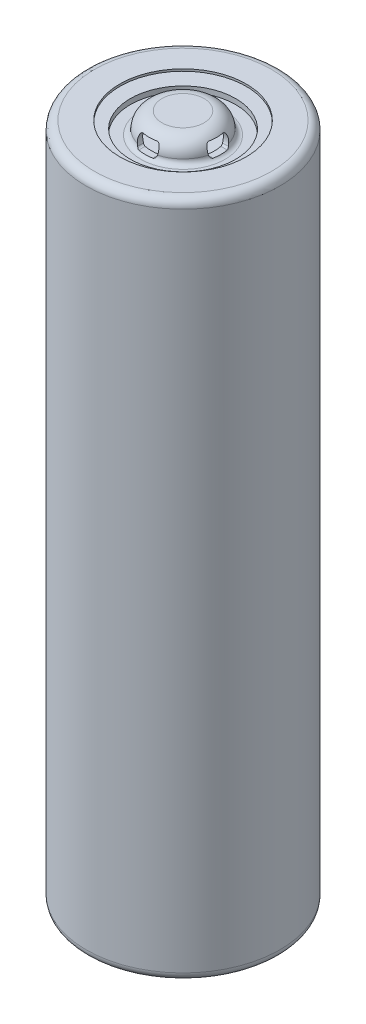
SolidWorks part; units mm, degrees
ref_plane "Front Plane" through (0, 0, 0) normal (0, 0, 1) x (1, 0, 0)
ref_plane "Top Plane" through (0, 0, 0) normal (0, 1, 0) x (1, 0, 0)
ref_plane "Right Plane" through (0, 0, 0) normal (1, 0, 0) x (0, 0, -1)
sketch "Sketch1" plane through (0, 0, 0) normal (0, 1, 0) x (1, 0, 0)
  circle A0 centre (0, 0) radius 9
  dimension "D1" = 18
extrude "Boss-Extrude1" add sketch "Sketch1" along normal blind 60
fillet "Fillet1" radius 1 2 edges at (0, 60, 9) (0, 0, 9)
sketch "Sketch2" plane through (0, 60, 0) normal (0, 1, 0) x (1, 0, 0)
  circle A0 centre (0, 0) radius 7
  dimension "D1" = 14
extrude "Boss-Extrude2" add sketch "Sketch2" along normal blind 2
fillet "Fillet2" radius 1 1 edges at (0, 62, 7)
sketch "Sketch4" plane through (0, 0, 0) normal (0, 0, 1) x (1, 0, 0)
  line L0 (0, 65) -> (3.5, 65)
  line L1 (3.5, 65) -> (3.5, 63)
  line L2 (3.5, 63) -> (8, 63)
  line L3 (8, 63) -> (8, 62)
  line L4 (6, 62) -> (-6, 62) construction
  line L5 (8, 62) -> (0, 62) construction
  line L6 (0, 62) -> (0, 65) construction
  line L7 (6, 62) -> (-6, 62) construction
  line L8 (0, 65) -> (0, 64.5) construction
  line L9 (0, 64.5) -> (3, 64.5)
  line L10 (3, 64.5) -> (3, 62.5)
  line L11 (3, 62.5) -> (5, 62.5)
  line L12 (5, 62.5) -> (5, 62)
  line L13 (5, 62) -> (8, 62) construction
  line L14 (5, 62) -> (8, 62)
  line L15 (0, 65) -> (0, 64.5)
  point P2 (1.75, 65)
  dimension "D1" = 65
  dimension "D2" = 8
  dimension "D3" = 3.5
  dimension "D4" = 2
  dimension "D5" = 0.5
  dimension "D6" = 0.5
  dimension "D7" = 0.5
  dimension "D8" = 3
revolve "Revolve1" add sketch "Sketch4" angle 360 about L6
fillet "Fillet3" radius 1.5 1 edges at (0, 65, -3.5)
fillet "Fillet4" radius 0.5 1 edges at (0, 63, -3.5)
fillet "Fillet5" radius 0.5 2 edges at (0, 62, -8) (0, 63, -8)
sketch "Sketch5" plane through (0, 0, 0) normal (0, 0, 1) x (1, 0, 0)
  line L0 (7.5, 63) -> (-7.5, 63) construction
  line L1 (8, 63.5) -> (5, 63.5)
  line L2 (8, 63.5) -> (8, 63)
  line L3 (8, 63) -> (5, 63)
  line L4 (5, 63.5) -> (5, 63)
  line L5 (0, 63) -> (0, 63.5) construction
  line L6 (0, 63.5) -> (5, 63.5) construction
  line L7 (0, 63) -> (5, 63) construction
  dimension "D1" = 0.5
  dimension "D2" = 5
revolve "Revolve2 isolation" add sketch "Sketch5" angle 360 about L5
sketch "Sketch6" plane through (0, 0, 0) normal (1, 0, 0) x (0, 0, -1)
  line L0 (7, 62) -> (7, 61)
  line L1 (7, 61) -> (8.8, 61)
  line L2 (8.8, 61) -> (8.8, 64)
  line L3 (8.8, 64) -> (7, 64)
  line L4 (7, 64) -> (7, 63.5)
  line L5 (8, 63.5) -> (-8, 63.5) construction
  line L6 (7, 63.5) -> (8.5, 63.5)
  line L7 (8.5, 63.5) -> (8.5, 61.3)
  line L10 (0, 0) -> (0, 65) construction
  line L11 (2, 65) -> (-2, 65) construction
  line L12 (7, 62) -> (7.3, 62)
  line L13 (7.3, 62) -> (7.3, 61.3)
  line L14 (7.3, 61.3) -> (8.5, 61.3)
  line L15 (8, 60) -> (-8, 60) construction
  point P3 (8.2057, 60.5263)
  dimension "D1" = 0.3
  dimension "D2" = 0.3
  dimension "D3" = 1
  dimension "D4" = 7
  dimension "D5" = 0.3
  dimension "D6" = 8.8
  dimension "D7" = 1
revolve "Revolve4 crimp" add sketch "Sketch6" angle 360 about L10
fillet "Fillet6" radius 0.8 3 edges at (0, 61, -8.8) (0, 64, -8.8) (0, 64, -7)
fillet "Fillet7" radius 0.3 1 edges at (0, 61, -7)
sketch "Sketch7" plane through (0, 0, 0) normal (1, 0, 0) x (0, 0, -1)
  line L0 (2, 65) -> (-2, 65) construction
  line L1 (0, 65) -> (0, 0) construction
  line L3 (-0.8, 63.2) -> (0.8, 63.2)
  line L4 (-0.3603, 63.2377) -> (-0.3603, 63.9235) construction
  line L5 (-0.8, 64.4) -> (0.8, 64.4)
  line L6 (1, 63.4571) -> (1, 65.3608) construction
  line L7 (-0.3603, 63.2377) -> (1, 65.3608) construction
  line L8 (-0.3603, 63.9235) -> (1, 63.4571) construction
  circle A1 centre (0, 63.8) radius 1 construction
  arc A2 (-0.8, 64.4) -> (-0.8, 63.2) centre (0, 63.8) ccw
  arc A3 (0.8, 64.4) -> (0.8, 63.2) centre (0, 63.8) cw
  dimension "D1" = 2
  dimension "D2" = 1.2
  dimension "D3" = 1.2
  dimension "D4" = 0.6
extrude "Cut-Extrude1" cut sketch "Sketch7" against normal blind 4
fillet "Fillet8" radius 0.25 4 edges at (-2.9949, 64.4, 0.8) (-2.9949, 64.4, -0.8) (-3.2007, 63.2, -0.8) (-3.2007, 63.2, 0.8)
pattern_circular "CirPattern1" count 4 over 360 about axis through (0, 63.5, 0) along (0, -1, 0) of "Cut-Extrude1", "Fillet8"
sketch "Sketch8" plane through (0, 0, 0) normal (1, 0, 0) x (0, 0, -1)
  line L0 (6, 64) -> (9, 64)
  line L1 (9, 64) -> (9, 0)
  line L2 (9, 0) -> (6, 0)
  line L3 (6, 0) -> (6, -0.2)
  line L4 (6, -0.2) -> (9.2, -0.2)
  line L5 (9.2, -0.2) -> (9.2, 64.2)
  line L6 (9.2, 64.2) -> (6, 64.2)
  line L7 (6, 64.2) -> (6, 64)
  line L8 (8, 64) -> (-8, 64) construction
  line L9 (-8, 0) -> (8, 0) construction
  line L10 (9, 1) -> (9, 59) construction
  line L11 (0, 65) -> (0, 0) construction
  line L12 (2, 65) -> (-2, 65) construction
  point P12 (7.5, 0)
  dimension "D1" = 0.2
  dimension "D2" = 0.2
  dimension "D3" = 6
revolve "Revolve5 wrap" add sketch "Sketch8" angle 360 about L11
fillet "Fillet9" radius 0.8 4 edges at (0, 64.2, 9.2) (0, -0.2, 9.2) (0, 64, 9) (0, 0, 9)
